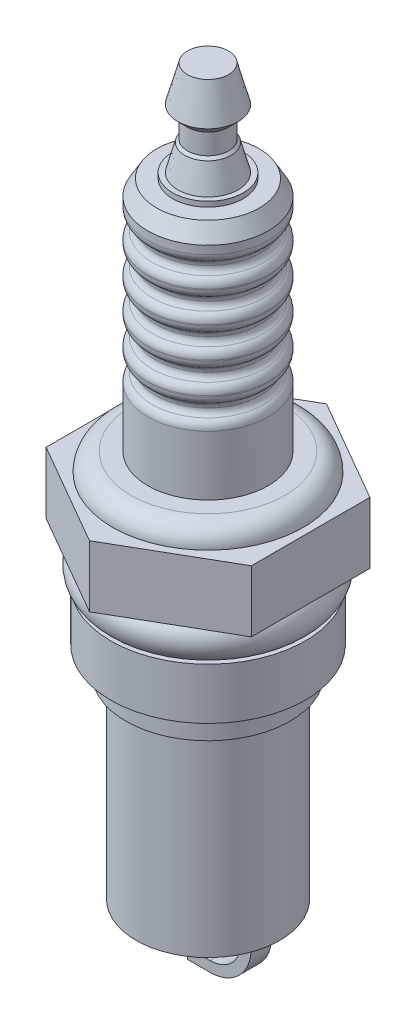
SolidWorks part; units mm, degrees
ref_plane "Plano frontal" through (0, 0, 0) normal (0, 0, 1) x (1, 0, 0)
ref_plane "Plano superior" through (0, 0, 0) normal (0, 1, 0) x (1, 0, 0)
ref_plane "Plano direito" through (0, 0, 0) normal (1, 0, 0) x (0, 0, -1)
sketch "Sketch1" plane through (0, 0, 0) normal (1, 0, 0) x (0, 0, -1)
  line L0 (0, 0) -> (0.5, 0)
  line L1 (0.5, 0) -> (0.5, 0.5)
  line L2 (0.5, 0.5) -> (0.75, 0.75)
  line L3 (0.75, 0.75) -> (0.75, 1.596)
  line L4 (0.75, 1.596) -> (2, 1.596)
  line L5 (2, 1.596) -> (2, 2.596)
  line L6 (2, 2.596) -> (7, 2.596)
  line L7 (7, 2.596) -> (7, 21.596)
  line L8 (0, 0) -> (0, 40.396)
  line L9 (7, 21.596) -> (8, 21.596)
  line L10 (8, 21.596) -> (8, 24.096)
  line L15 (9.3, 38.596) -> (9.3, 40.396)
  line L16 (9.3, 40.396) -> (0, 40.396)
  line L17 (8, 24.096) -> (9.4682, 24.096)
  line L18 (9.4682, 24.096) -> (9.4682, 29.096)
  line L19 (9.4682, 29.096) -> (8.9682, 29.096)
  line L20 (8.9682, 32.596) -> (12.3, 32.596)
  line L21 (12.3, 32.596) -> (12.3, 38.596)
  line L22 (12.3, 38.596) -> (9.3, 38.596)
  line L23 (0, 30.846) -> (10, 30.846) construction
  arc A1 (8.9682, 32.596) -> (8.9682, 29.096) centre (8, 30.846) cw
  point P18 (8, 22.846)
  point P22 (0, 0)
  dimension "D18" = 2
  dimension "D1" = 0.5
  dimension "D2" = 45
  dimension "D3" = 0.5
  dimension "D4" = 0.75
  dimension "D5" = 1
  dimension "D6" = 2
  dimension "D7" = 19
  dimension "D8" = 7
  dimension "D9" = 8
  dimension "D10" = 2.5
  dimension "D11" = 5
  dimension "D12" = 3.5
  dimension "D13" = 1.8
  dimension "D14" = 6
  dimension "D15" = 12.3
  dimension "D16" = 10
  dimension "D17" = 0.5
  dimension "D19" = 3
revolve "Revolve1" add sketch "Sketch1" angle 360 about L8
sketch "Sketch2" plane through (0, 2.596, 0) normal (0, -1, 0) x (1, 0, 0)
  circle A0 centre (0, 0) radius 3.75
  circle A1 centre (0, 0) radius 2 construction
  circle A2 centre (0, 0) radius 2
  dimension "D1" = 7.5
extrude "Cut-Extrude1" cut sketch "Sketch2" against normal blind 17
fillet "Fillet1" radius 0.5 1 edges at (0, 1.596, -2)
sketch "Sketch3" plane through (0, 0, 0) normal (1, 0, 0) x (0, 0, -1)
  line L0 (0, 40.396) -> (0, 94.5206) construction
  line L1 (9.3, 40.396) -> (-9.3, 40.396) construction
  line L2 (0, 40.396) -> (5.866, 40.396)
  line L3 (5.866, 40.396) -> (5.866, 46.896)
  line L4 (5.866, 46.896) -> (5.106, 46.896)
  line L5 (5.106, 46.896) -> (5.106, 48.396)
  line L6 (5.106, 48.396) -> (5.866, 48.396)
  line L7 (5.866, 48.396) -> (5.866, 49.896)
  line L8 (5.866, 49.896) -> (5.106, 49.896)
  line L9 (5.106, 49.896) -> (5.106, 51.396)
  line L10 (5.106, 51.396) -> (5.866, 51.396)
  line L11 (5.866, 51.396) -> (5.866, 52.896)
  line L12 (5.866, 52.896) -> (5.106, 52.896)
  line L13 (5.106, 52.896) -> (5.106, 54.396)
  line L14 (5.106, 54.396) -> (5.866, 54.396)
  line L15 (5.866, 54.396) -> (5.866, 55.896)
  line L16 (5.866, 55.896) -> (5.106, 55.896)
  line L17 (5.106, 55.896) -> (5.106, 57.396)
  line L18 (5.106, 57.396) -> (5.866, 57.396)
  line L19 (5.866, 57.396) -> (5.866, 58.896)
  line L20 (5.866, 58.896) -> (5.106, 58.896)
  line L21 (5.106, 58.896) -> (5.106, 60.396)
  line L22 (5.106, 60.396) -> (5.866, 60.396)
  line L23 (5.866, 60.396) -> (5.866, 61.896)
  line L24 (5.866, 61.896) -> (5, 63.396)
  line L25 (5, 63.396) -> (3.4378, 63.396)
  line L26 (3.4378, 63.396) -> (3.4378, 63.896)
  line L27 (3.4378, 63.896) -> (2.9378, 63.896)
  line L28 (2.9378, 63.896) -> (2.25, 66.463)
  line L29 (2.25, 66.463) -> (2, 66.713)
  line L30 (2, 66.713) -> (2, 68.713)
  line L31 (2, 68.713) -> (2.9378, 69.6508)
  line L32 (2.9378, 69.6508) -> (2, 73.1508)
  line L33 (2, 73.1508) -> (0, 73.1508)
  line L34 (2.9378, 69.6508) -> (2.9378, 63.896) construction
  line L35 (0, 73.1508) -> (0, 40.396)
  point P33 (2.5914, 67.064)
  point P38 (0, 0)
  point P39 (2.4887, 66.5525)
  point P40 (0, 0)
  point P41 (2, 66.9895)
  point P42 (2.3827, 65.9679)
  point P43 (2.5976, 65.1659)
  dimension "D1" = 23
  dimension "D2" = 5
  dimension "D3" = 3
  dimension "D4" = 1.5
  dimension "D5" = 30
  dimension "D6" = 1.5
  dimension "D8" = 0.76
  dimension "D9" = 0.5
  dimension "D10" = 0.5
  dimension "D11" = 2
  dimension "D12" = 2
  dimension "D13" = 15
  dimension "D14" = 120
  dimension "D15" = 3.5
  dimension "D16" = 2
  dimension "D17" = 0.25
revolve "Revolve2" add sketch "Sketch3" angle 360 about L35
fillet "Fillet2" radius 0.74 10 edges at (0, 46.896, 5.106) (0, 48.396, 5.106) (0, 52.896, 5.106) (0, 51.396, 5.106) (0, 54.396, 5.106) (0, 55.896, 5.106) (0, 57.396, 5.106) (0, 58.896, 5.106) (0, 60.396, 5.106) (0, 49.896, 5.106)
fillet "Fillet3" radius 1 10 edges at (0, 46.896, 5.866) (0, 49.896, 5.866) (0, 51.396, 5.866) (0, 52.896, 5.866) (0, 54.396, 5.866) (0, 55.896, 5.866) (0, 58.896, 5.866) (0, 57.396, 5.866) (0, 60.396, 5.866) (0, 48.396, 5.866)
fillet "Fillet4" radius 1.8 1 edges at (0, 40.396, -9.3)
sketch "Sketch5" plane through (0, 0, 0) normal (0, 0, 1) x (1, 0, 0)
  line L0 (4.2, 2.596) -> (4.2, 1.5)
  line L1 (-7, 2.596) -> (7, 2.596) construction
  line L2 (1.2, -1.5) -> (-0.98, -1.5)
  line L3 (-0.98, -1.5) -> (-0.98, -2.5)
  line L4 (-0.98, -2.5) -> (1.2, -2.5)
  line L5 (5.2, 1.5) -> (5.2, 2.596)
  line L6 (4.2, 2.596) -> (5.2, 2.596)
  arc A0 (4.2, 1.5) -> (1.2, -1.5) centre (1.2, 1.5) cw
  arc A1 (1.2, -2.5) -> (5.2, 1.5) centre (1.2, 1.5) ccw
  point P13 (5.2, -2.5)
  dimension "D6" = 3
  dimension "D7" = 4
  dimension "D1" = 1
  dimension "D2" = 1
  dimension "D3" = 0.98
  dimension "D4" = 1.5
  dimension "D5" = 5.2
extrude "Boss-Extrude1" add sketch "Sketch5" along normal mid plane 2
sketch "Sketch6" plane through (0, 38.596, 0) normal (0, 1, 0) x (1, 0, 0)
  line L1 (0, -11.547) -> (10, -5.7735)
  line L2 (10, -5.7735) -> (10, 5.7735)
  line L3 (10, 5.7735) -> (0, 11.547)
  line L4 (0, 11.547) -> (-10, 5.7735)
  line L5 (-10, 5.7735) -> (-10, -5.7735)
  line L6 (-10, -5.7735) -> (0, -11.547)
  circle A0 centre (0, 0) radius 10 construction
  dimension "D1" = 20
extrude "Cut-Extrude2" cut sketch "Sketch6" against normal up to surface (6 mm away) flip side to cut up to face at (0, 32.596, -12.3)
